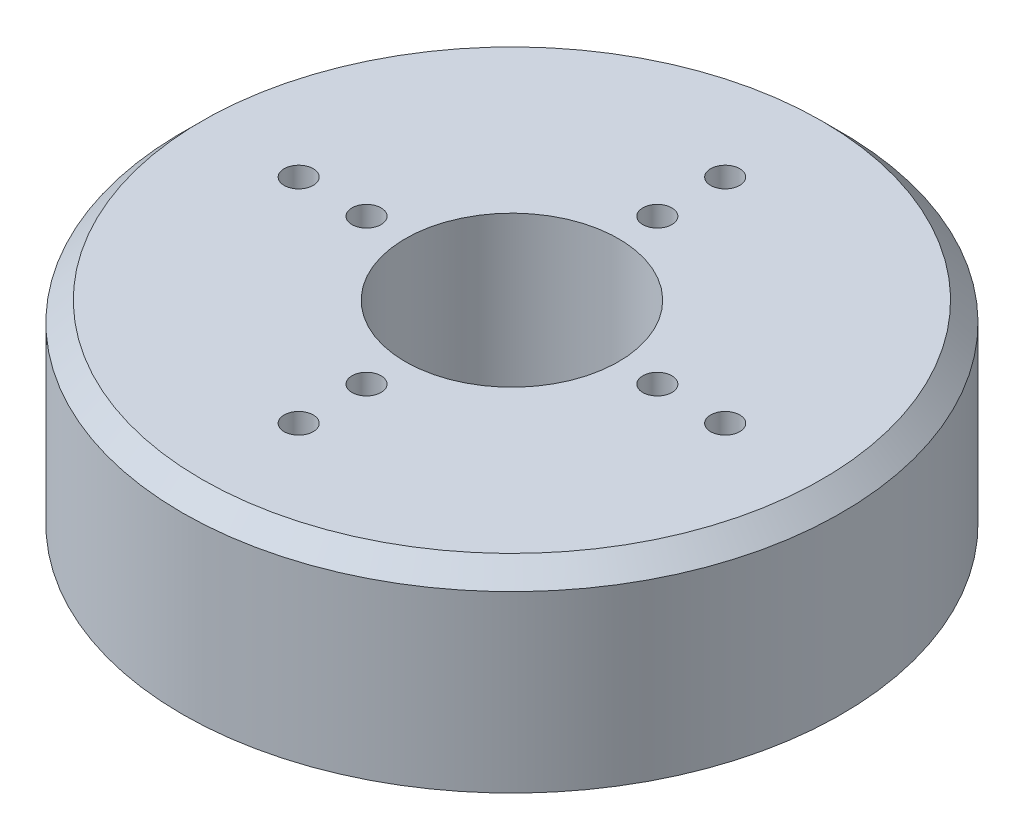
SolidWorks part; units mm, degrees
ref_plane "前视基准面" through (0, 0, 0) normal (0, 0, 1) x (1, 0, 0)
ref_plane "上视基准面" through (0, 0, 0) normal (0, 1, 0) x (1, 0, 0)
ref_plane "右视基准面" through (0, 0, 0) normal (1, 0, 0) x (0, 0, -1)
sketch "草图1" plane through (0, 0, 0) normal (0, 1, 0) x (1, 0, 0)
  circle A0 centre (0, 0) radius 34
  circle A1 centre (0, 0) radius 30
  dimension "D1" = 68
  dimension "D2" = 60
extrude "凸台-拉伸1" add sketch "草图1" along normal blind 20
extrude "凸台-拉伸2" add sketch "草图1<2>" against normal blind 4 from surface contours A1 | A0 A1 region at (-33.0383, 0, 0) region at (0, 0, 0) starting at face at (0, 20, 34)
sketch "草图1<2>" plane through (0, 0, 0) normal (0, 1, 0) x (1, 0, 0) same geometry as "草图1"
sketch "草图2" plane through (0, 20, 0) normal (0, 1, 0) x (1, 0, 0)
  circle A0 centre (0, 0) radius 11
  circle A1 centre (0, 0) radius 15 construction
  circle A2 centre (0, 0) radius 22 construction
  circle A4 centre (0, 15) radius 1.5
  circle A5 centre (0, 22) radius 1.5
  circle A6 centre (15, 0) radius 1.5
  circle A7 centre (22, 0) radius 1.5
  circle A8 centre (0, -15) radius 1.5
  circle A9 centre (0, -22) radius 1.5
  circle A10 centre (-15, 0) radius 1.5
  circle A11 centre (-22, 0) radius 1.5
  point P24 (0, 0)
  dimension "D1" = 22
  dimension "D2" = 30
  dimension "D3" = 44
  dimension "D4" = 3
  dimension "D5" = 3
  dimension "D6" = 4
extrude "切除-拉伸1" cut sketch "草图2" against normal through all
chamfer "倒角1" distance 2 angle 45 1 edges at (0, 20, 34)
sketch "草图3" plane through (0, 16, 0) normal (0, -1, 0) x (1, 0, 0)
  circle A0 centre (0, 0) radius 12.5
  circle A1 centre (0, 0) radius 11 construction
  circle A2 centre (0, 0) radius 11
  circle M11 centre (0, 0) radius 11
  dimension "D1" = 25
extrude "凸台-拉伸3" add sketch "草图3" along normal up to surface (16 mm away) up to face at (0, 0, 34)
extrude "凸台-拉伸4" add sketch "草图3<2>" against normal blind 3 from surface contours M11 | A0 M11 region at (-12.1464, 16, 0) region at (0, 16, 0) starting at face at (0, 0, 11)
sketch "草图3<2>" plane through (0, 16, 0) normal (0, -1, 0) x (1, 0, 0) same geometry as "草图3"
sketch "草图5" plane through (0, 3, 0) normal (0, 1, 0) x (1, 0, 0)
  circle A0 centre (0, 0) radius 2.5
  dimension "D1" = 5
extrude "切除-拉伸2" cut sketch "草图5" against normal through all
sketch "草图6" plane through (0, 16, 0) normal (0, -1, 0) x (1, 0, 0)
  circle A0 centre (0, 0) radius 12.5 construction
  circle A1 centre (0, 0) radius 30 construction
  circle A2 centre (0, 0) radius 12.5
  circle A3 centre (0, 0) radius 30
extrude "凸台-拉伸5" add sketch "草图6" along normal blind 3 from offset 3
